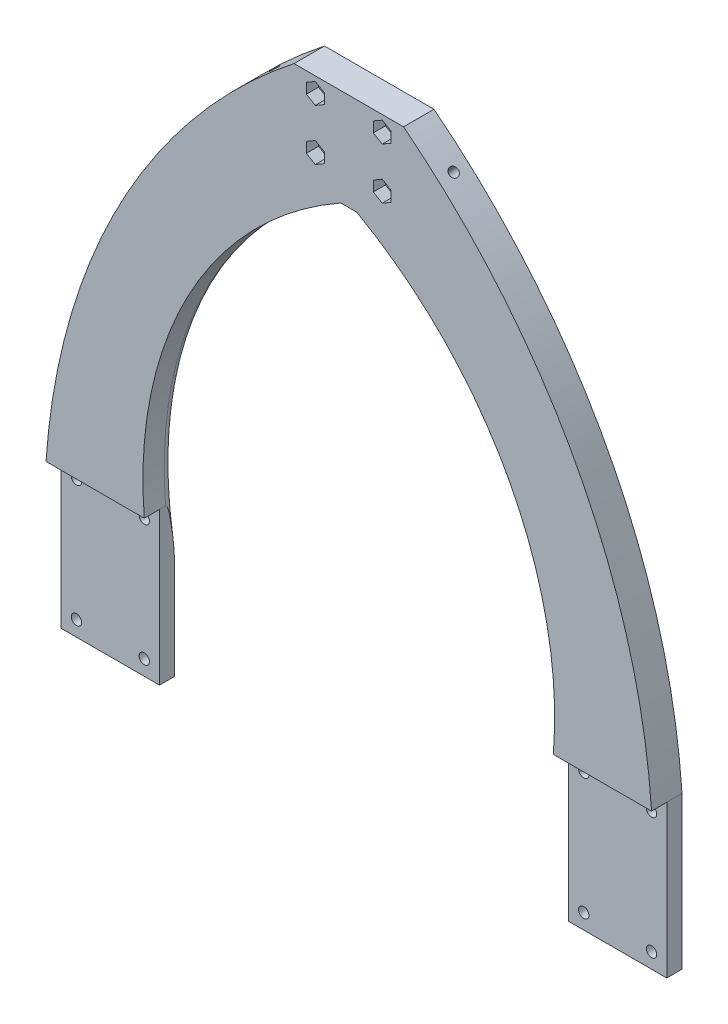
SolidWorks part; units mm, degrees
ref_plane "Ebene vorne" through (0, 0, 0) normal (0, 0, 1) x (1, 0, 0)
ref_plane "Ebene oben" through (0, 0, 0) normal (0, 1, 0) x (1, 0, 0)
ref_plane "Ebene rechts" through (0, 0, 0) normal (1, 0, 0) x (0, 0, -1)
sketch "Skizze1" plane through (0, 0, 0) normal (0, 1, 0) x (1, 0, 0)
  line L1 (-99.5, -210) -> (99.5, -210)
  line L2 (-99.5, -210) -> (-99.5, 210)
  line L3 (-99.5, 210) -> (99.5, 210)
  line L4 (99.5, -210) -> (99.5, 210)
  line L5 (-99.5, -210) -> (99.5, 210) construction
  line L6 (-99.5, 210) -> (99.5, -210) construction
  point P0 (0, 0)
  dimension "D1" = 199
  dimension "D2" = 420
extrude "Aufsatz-Linear austragen1" add sketch "Skizze1" along normal blind 10
ref_plane "Ebene1" through (0, -97.5366, 81.8429) normal (0, -0.766, 0.6428) x (1, 0, 0)
sketch "Skizze2" plane through (0, -97.5366, 81.8429) normal (0, -0.766, 0.6428) x (1, 0, 0)
  line L1 (-99.5, 167.2972) -> (99.5, 167.2972) construction
  circle A0 centre (0, 147.2972) radius 5
  dimension "D1" = 10
  dimension "D2" = 20
extrude "Schnitt-Linear austragen1" [suppressed] cut sketch "Skizze2" against normal blind 30 and the other way blind 10
sketch "Skizze3" [suppressed] plane through (0, -67.9923, 57.0523) normal (0, -0.766, 0.6428) x (1, 0, 0)
  circle A0 centre (0, 101.3345) radius 5
  dimension "D1" = 10
extrude "Aufsatz-Linear austragen2" [suppressed] add sketch "Skizze3" along normal blind 0.1
sketch "Skizze4" plane through (0, -97.5366, 81.8429) normal (0, -0.766, 0.6428) x (1, 0, 0)
  line L0 (0, 167.2972) -> (0, 159.9002) construction
  line L1 (-99.5, 167.2972) -> (99.5, 167.2972) construction
  line L2 (-25, 167.2972) -> (-25, 202.2972)
  line L3 (-25, 202.2972) -> (25, 202.2972)
  line L4 (-25, 167.2972) -> (25, 167.2972)
  line L5 (25, 167.2972) -> (25, 202.2972)
  point P10 (0, 202.2972)
  dimension "D1" = 50
  dimension "D2" = 35
extrude "Aufsatz-Linear austragen3" [suppressed] add sketch "Skizze4" against normal blind 10 separate body
sketch "Skizze5" plane through (0, 10, 0) normal (0, 1, 0) x (1, 0, 0)
  line L0 (0, 0) -> (0, -210) construction
  line L1 (-99.5, -210) -> (99.5, -210) construction
  line L2 (99.5, -210) -> (18, -210)
  line L3 (-18, -210) -> (-99.5, -56)
  line L4 (-99.5, 210) -> (-99.5, -210) construction
  line L5 (-99.5, -56) -> (-99.5, -210)
  line L6 (-99.5, -210) -> (-18, -210)
  line L7 (99.5, -56) -> (99.5, -210)
  line L8 (18, -210) -> (99.5, -56)
  line L9 (-99.5, 210) -> (-99.5, 125)
  line L10 (-99.5, 125) -> (99.5, 125)
  line L11 (99.5, -210) -> (99.5, 210) construction
  line L12 (99.5, 125) -> (99.5, 210)
  line L13 (99.5, 210) -> (-99.5, 210)
  line L14 (67.211, -56) -> (-67.211, -56)
  line L15 (-67.211, -56) -> (-2.6461, -178)
  line L16 (67.211, -56) -> (2.6461, -178)
  line L17 (-2.6461, -178) -> (2.6461, -178)
  line L18 (2.6461, -178) -> (0, -183) construction
  line L19 (-2.6461, -178) -> (0, -183) construction
  point P27 (0, -56)
  dimension "D1" = 36
  dimension "D2" = 154
  dimension "D3" = 85
  dimension "D4" = 32
  dimension "D5" = 27
extrude "Schnitt-Linear austragen2" cut sketch "Skizze5" against normal blind 10
sketch "Skizze6" plane through (0, 10, 0) normal (0, 1, 0) x (1, 0, 0)
  line L0 (0, -210) -> (0, -178) construction
  line L1 (-18, -210) -> (18, -210) construction
  line L2 (-2.6461, -178) -> (2.6461, -178) construction
  line L3 (0, -196.59) -> (-21.075, -196.59) construction
  circle A0 centre (-11, -205) radius 1.7
  circle A1 centre (-11, -188.18) radius 1.7
  circle A2 centre (11, -205) radius 1.7
  circle A3 centre (11, -188.18) radius 1.7
  dimension "D1" = 3.4
  dimension "D2" = 11
  dimension "D3" = 5
  dimension "D4" = 13.41
extrude "Schnitt-Linear austragen3" cut sketch "Skizze6" against normal through all
sketch "Skizze7" plane through (0, 0, 0) normal (0, -1, 0) x (1, 0, 0)
  line L0 (-11, 205) -> (-11, 210) construction
  line L1 (-18, 210) -> (18, 210) construction
  line L2 (-11, 205) -> (-5.1092, 205) construction
  line L3 (-11, 208.4064) -> (-8.05, 206.7032)
  line L4 (-8.05, 206.7032) -> (-8.05, 203.2968)
  line L5 (-11, 201.5936) -> (-8.05, 203.2968)
  line L6 (-11, 201.5936) -> (-13.95, 203.2968)
  line L7 (-13.95, 206.7032) -> (-13.95, 203.2968)
  line L8 (-11, 208.4064) -> (-13.95, 206.7032)
  line L9 (0, 210) -> (0, 121.6034) construction
  line L10 (11, 205) -> (11, 188.18) construction
  line L11 (11, 196.59) -> (0, 196.59) construction
  line L12 (11, 208.4064) -> (8.05, 206.7032)
  line L13 (11, 201.5936) -> (8.05, 203.2968)
  line L14 (8.05, 206.7032) -> (8.05, 203.2968)
  line L15 (11, 201.5936) -> (13.95, 203.2968)
  line L16 (13.95, 206.7032) -> (13.95, 203.2968)
  line L17 (11, 208.4064) -> (13.95, 206.7032)
  line L18 (-8.05, 186.4768) -> (-8.05, 189.8832)
  line L19 (-11, 191.5864) -> (-13.95, 189.8832)
  line L20 (-11, 191.5864) -> (-8.05, 189.8832)
  line L21 (-13.95, 186.4768) -> (-13.95, 189.8832)
  line L22 (-11, 184.7736) -> (-13.95, 186.4768)
  line L23 (-11, 184.7736) -> (-8.05, 186.4768)
  line L24 (8.05, 186.4768) -> (8.05, 189.8832)
  line L25 (11, 191.5864) -> (8.05, 189.8832)
  line L26 (11, 191.5864) -> (13.95, 189.8832)
  line L27 (13.95, 186.4768) -> (13.95, 189.8832)
  line L28 (11, 184.7736) -> (13.95, 186.4768)
  line L29 (11, 184.7736) -> (8.05, 186.4768)
  point P10 (-8.05, 205)
  dimension "D1" = 120
  dimension "D2" = 5.9
extrude "Schnitt-Linear austragen4" cut sketch "Skizze7" against normal blind 4
sketch "Skizze8" plane through (0, 10, 0) normal (0, 1, 0) x (1, 0, 0)
  line L0 (99.5, 115.41) -> (78.872, 115.41) construction
  line L1 (99.5, -56) -> (99.5, 125) construction
  line L2 (-99.5, 125) -> (99.5, 125) construction
  dimension "D1" = 9.59
ref_plane "Ebene2" through (0, 62.6966, -52.6087) normal (0, 0.766, -0.6428) x (-1, 0, 0)
sketch "Skizze9" plane through (0, 62.6966, -52.6087) normal (0, 0.766, -0.6428) x (-1, 0, 0)
  line L0 (-99.5, -81.9813) -> (-78.872, -81.9813) construction
  line L1 (-99.5, 49.3264) -> (-99.5, -89.3277) construction
  line L2 (0, -45.2589) -> (0, -16.2619) construction
  circle A0 centre (-94.5, -81.9813) radius 1.7
  circle A1 centre (94.5, -81.9813) radius 1.7
  circle A2 centre (-30, -81.9813) radius 1.7
  circle A3 centre (30, -81.9813) radius 1.7
  dimension "D1" = 3.4
  dimension "D2" = 5
  dimension "D3" = 30
extrude "Schnitt-Linear austragen5" [suppressed] cut sketch "Skizze9" against normal through all and the other way through all
ref_plane "Ebene3" through (0, 55.0361, -46.1808) normal (0, 0.766, -0.6428) x (-1, 0, 0)
sketch "Skizze10" [suppressed] plane through (0, 55.0361, -46.1808) normal (0, 0.766, -0.6428) x (-1, 0, 0)
  line L0 (-95, -81.9813) -> (-100, -81.9813) construction
  line L1 (-95, -81.9813) -> (-95, -30.0694) construction
  line L2 (-95, -78.7482) -> (-97.8, -80.3647)
  line L3 (-97.8, -80.3647) -> (-97.8, -83.5979)
  line L4 (-95, -85.2145) -> (-97.8, -83.5979)
  line L5 (-95, -85.2145) -> (-92.2, -83.5979)
  line L6 (-92.2, -80.3647) -> (-92.2, -83.5979)
  line L7 (-95, -78.7482) -> (-92.2, -80.3647)
  line L8 (0, 0) -> (0, -45.6283) construction
  line L9 (-30, -81.9813) -> (-95, -81.9813) construction
  line L10 (-62.5, -81.9813) -> (-62.5, -23.1343) construction
  line L11 (-32.8, -80.3647) -> (-32.8, -83.5979)
  line L12 (-30, -85.2145) -> (-32.8, -83.5979)
  line L13 (-30, -85.2145) -> (-27.2, -83.5979)
  line L14 (-27.2, -80.3647) -> (-27.2, -83.5979)
  line L15 (-30, -78.7482) -> (-27.2, -80.3647)
  line L16 (-30, -78.7482) -> (-32.8, -80.3647)
  line L17 (95, -78.7482) -> (92.2, -80.3647)
  line L18 (92.2, -80.3647) -> (92.2, -83.5979)
  line L19 (95, -85.2145) -> (92.2, -83.5979)
  line L20 (95, -85.2145) -> (97.8, -83.5979)
  line L21 (97.8, -80.3647) -> (97.8, -83.5979)
  line L22 (95, -78.7482) -> (97.8, -80.3647)
  line L23 (30, -78.7482) -> (32.8, -80.3647)
  line L24 (30, -78.7482) -> (27.2, -80.3647)
  line L25 (27.2, -80.3647) -> (27.2, -83.5979)
  line L26 (30, -85.2145) -> (27.2, -83.5979)
  line L27 (30, -85.2145) -> (32.8, -83.5979)
  line L28 (32.8, -80.3647) -> (32.8, -83.5979)
  point P9 (-97.8, -81.9813)
  point P31 (97.8, -81.9813)
  dimension "D1" = 120
  dimension "D2" = 5.6
extrude "Schnitt-Linear austragen6" [suppressed] cut sketch "Skizze10" against normal blind 10 and the other way blind 5
sketch "Skizze13" plane through (0, 10, 0) normal (0, 1, 0) x (1, 0, 0)
  line L0 (67.211, -56) -> (99.5, -56) construction
  line L1 (67.211, -56) -> (92.4353, -69.3492) construction
  line L2 (99.5, -56) -> (18, -210) construction
  line L3 (0, 0) -> (0, -38.1435) construction
  line L4 (2.6461, -178) -> (67.211, -56) construction
  line L5 (79.8232, -62.6746) -> (103.8351, -17.3024) construction
  line L6 (99.5, -56) -> (99.5, 125) construction
  line L7 (83.3555, -56) -> (83.3555, -1) construction
  line L8 (93.5, -58.8065) -> (101.0692, -44.504) construction
  line L9 (83.1285, -86.935) -> (57.9043, -73.5858) construction
  line L10 (71.7911, -80.935) -> (86.3039, -80.935) construction
  circle A0 centre (93.5, -58.8065) radius 1.7
  circle A1 centre (72.5142, -58.8065) radius 1.7
  circle A2 centre (81.7891, -80.935) radius 1.7
  circle A3 centre (-81.7891, -80.935) radius 1.7
  circle A4 centre (-93.5, -58.8065) radius 1.7
  circle A5 centre (-72.5142, -58.8065) radius 1.7
  dimension "D1" = 6
  dimension "D5" = 35
  dimension "D3" = 3.4
  dimension "D6" = 3.4
  dimension "D2" = 6
  dimension "D4" = 6
extrude "Schnitt-Linear austragen7" [suppressed] cut sketch "Skizze13" against normal through all
sketch "Skizze14" plane through (100.8819, 0, 53.3888) normal (0.8839, 0, 0.4678) x (0.4678, 0, -0.8839)
  line L0 (-37.9543, 5) -> (-37.9543, 10)
  line L5 (-2.9543, 0) -> (-2.9543, 10) construction
  line L6 (-37.9543, 5) -> (-2.9543, 5)
  line L7 (-2.9543, 10) -> (-177.1905, 10) construction
  line L8 (-37.9543, 10) -> (-2.9543, 10)
  line L9 (-2.9543, 10) -> (-2.9543, 5)
  dimension "D1" = 35
extrude "Schnitt-Linear austragen8" [suppressed] cut sketch "Skizze14" against normal up to surface (28.9525 mm away)
mirror "Spiegeln1" [suppressed] about plane through (0, 0, 0) normal (1, 0, 0)
sketch "Skizze15" [suppressed] plane through (95, 0, 0) normal (1, 0, 0) x (0, 0, -1)
  line L0 (4, 10) -> (4, 0)
  line L1 (4, 0) -> (65, 0)
  line L2 (65, 0) -> (65, 10)
  line L3 (65, 10) -> (4, 10)
extrude "Schnitt-Linear austragen9" [suppressed] cut sketch "Skizze15" against normal through all
sketch "Skizze16" plane through (0, 0, 0) normal (0, -1, 0) x (1, 0, 0)
  line L0 (0, 210) -> (0, 178) construction
  line L1 (-18, 210) -> (18, 210) construction
  line L2 (-2.6461, 178) -> (2.6461, 178) construction
  line L3 (11, 196.59) -> (0, 196.59) construction
  line L4 (11, 205) -> (11, 188.18) construction
  line L6 (-17.5, 193.09) -> (17.5, 193.09)
  line L7 (-17.5, 193.09) -> (-17.5, 200.09)
  line L8 (-17.5, 200.09) -> (17.5, 200.09)
  line L9 (17.5, 193.09) -> (17.5, 200.09)
  line L10 (-17.5, 193.09) -> (17.5, 200.09) construction
  line L11 (-17.5, 200.09) -> (17.5, 193.09) construction
  dimension "D1" = 7
  dimension "D2" = 35
extrude "Schnitt-Linear austragen10" [suppressed] cut sketch "Skizze16" against normal blind 5
sketch "Skizze17" [suppressed] plane through (17.5, 0, 0) normal (-1, 0, 0) x (0, 0, 1)
  line L0 (196.59, 0) -> (196.59, 11.1261) construction
  line L1 (193.09, 0) -> (200.09, 0) construction
  line L2 (193.09, 5) -> (196.59, 8.5)
  line L3 (196.59, 8.5) -> (200.09, 5)
  line L4 (200.09, 5) -> (193.09, 5)
  dimension "D1" = 90
extrude "Schnitt-Linear austragen11" [suppressed] cut sketch "Skizze17" along normal up to surface (35 mm away)
sketch "Skizze18" [suppressed] plane through (0, 10, 0) normal (0, 1, 0) x (1, 0, 0)
  line L0 (0, -210) -> (0, 0) construction
  line L1 (-18, -210) -> (18, -210) construction
  line L2 (62.5765, -72.2325) -> (35.4483, -67.5372)
  line L3 (15.3378, -155.8503) -> (-22.1774, -134.6566)
  line L4 (2.8247, -178) -> (62.5765, -72.2325) construction
  line L5 (-15.3378, -155.8503) -> (22.1774, -134.6566)
  line L6 (58.6594, -79.166) -> (40.7308, -76.063)
  line L7 (0, -147.1854) -> (19.5429, -147.1854) construction
  line L8 (0, -95.4) -> (31.4297, -95.4) construction
  line L9 (11.6488, -162.3803) -> (0, -155.7995)
  line L10 (-71.7468, -56) -> (-2.8247, -178) construction
  line L11 (0, -95.4) -> (-37.5153, -116.5937) construction
  line L12 (-37.5153, -116.5937) -> (-39.2566, -117.5774) construction
  line L13 (-11.6488, -162.3803) -> (0, -155.7995)
  line L14 (-58.6594, -79.166) -> (-40.7308, -76.063)
  line L15 (-62.5765, -72.2325) -> (-35.4483, -67.5372)
  circle A0 centre (0, -95.4) radius 33.5
  arc A1 (7.4594, -151.3994) -> (7.4594, -142.9713) centre (9.84, -147.1854) cw
  arc A2 (-7.4594, -151.3994) -> (-7.4594, -142.9713) centre (-9.84, -147.1854) ccw
  circle A3 centre (0, -95.4) radius 45.0879
  point P17 (0, -147.1854)
  point P36 (5, -147.1854)
  point P40 (-5, -147.1854)
  line M16 (62.5765, -72.2325) -> (2.8247, -178)
  line M18 (-2.8247, -178) -> (-71.7468, -56)
  dimension "D2" = 67
  dimension "D5" = 2
  dimension "D4" = 10
  dimension "D1" = 114.6
  dimension "D3" = 7.5
  dimension "D6" = 7.5
extrude "Aufsatz-Linear austragen4" [suppressed] add sketch "Skizze18" against normal blind 10 contours A3 L15 L14 M18 | A3 A0 M16 M18 | A3 L6 L2 M16 | A2 L5 L3 | A3 L3 L5 | L3 A1 L5 | L13 L9 L3 L5 M18 M16
sketch "Skizze19" [suppressed] plane through (0, 0, 0) normal (0, -1, 0) x (1, 0, 0)
  circle A0 centre (0, 35.4) radius 31.5
  circle A1 centre (0, 35.4) radius 33.5
  circle A2 centre (0, 35.4) radius 33.5 construction
  dimension "D1" = 63
extrude "Aufsatz-Linear austragen5" [suppressed] add sketch "Skizze19" against normal blind 1
sketch "Skizze20" plane through (0, 10, 0) normal (0, 1, 0) x (1, 0, 0)
  line L0 (99.5, 119.52) -> (55.4083, 119.52) construction
  line L1 (99.5, -56) -> (99.5, 125) construction
  line L2 (-99.5, 125) -> (99.5, 125) construction
  line L3 (0, 125) -> (0, 96.9732) construction
  line L4 (105, 43.82) -> (35.5869, 43.82) construction
  circle A0 centre (90.5, 119.52) radius 1.7
  circle A1 centre (48.5, 119.52) radius 1.7
  circle A2 centre (-48.5, 119.52) radius 1.7
  circle A3 centre (-90.5, 119.52) radius 1.7
  circle A4 centre (87, 43.82) radius 1.7
  circle A5 centre (52, 43.82) radius 1.7
  circle A6 centre (-87, 43.82) radius 1.7
  circle A7 centre (-52, 43.82) radius 1.7
  dimension "D1" = 3.4
  dimension "D2" = 5.48
  dimension "D3" = 9
  dimension "D4" = 42
  dimension "D5" = 75.7
  dimension "D6" = 12.5
  dimension "D7" = 35
extrude "Schnitt-Linear austragen12" cut sketch "Skizze20" against normal through all
sketch "Skizze21" plane through (0, 10, 0) normal (0, 1, 0) x (1, 0, 0)
  line L0 (-67.211, -56) -> (-67.211, 19)
  line L1 (-67.211, 19) -> (67.211, 19)
  line L2 (67.211, 19) -> (67.211, -56)
  line L3 (67.211, -56) -> (-67.211, -56) construction
  line L4 (-67.211, -56) -> (67.211, -56)
  dimension "D1" = 75
extrude "Schnitt-Linear austragen13" cut sketch "Skizze21" against normal through all
sketch "Skizze22" plane through (0, 10, 0) normal (0, 1, 0) x (1, 0, 0)
  line L0 (-67.211, -56) -> (-2.6461, -178)
  arc A0 (-67.211, -56) -> (-2.6461, -178) centre (60.0769, -66.7211) ccw
  line M19 (-2.6461, -178) -> (-67.211, -56)
extrude "Schnitt-Linear austragen14" cut sketch "Skizze22" against normal through all contours M19 region at (-42.1385, 10, 120.8156)
sketch "Skizze23" plane through (0, 10, 0) normal (0, 1, 0) x (1, 0, 0)
  line L0 (-18, -210) -> (-99.5, -56) construction
  line L1 (-99.5, -56) -> (-18, -210)
  arc A0 (-18, -210) -> (-99.5, -56) centre (114.4449, -41.3416) cw
  arc A2 (-67.211, -56) -> (-2.6461, -178) centre (60.0769, -66.7211) ccw construction
  dimension "D1" = 60
extrude "Aufsatz-Linear austragen6" add sketch "Skizze23" against normal blind 10
mirror "Spiegeln2" about plane through (0, 0, 0) normal (1, 0, 0) of "Aufsatz-Linear austragen6", "Schnitt-Linear austragen14"
sketch "Skizze25" plane through (0, 10, 0) normal (0, 1, 0) x (1, 0, 0)
  line L0 (-99.5, -56) -> (-67.211, -56) construction
  line L1 (-99.5, -6) -> (-99.5, -56) construction
  line L2 (-99.5, -6) -> (-67.211, -6) construction
  line L3 (-67.211, 19) -> (-67.211, -56) construction
  line L4 (-83.3555, -6) -> (-83.3555, -56) construction
  line L5 (-99.5, -31) -> (-67.211, -31) construction
  line L6 (-99.5, 125) -> (-99.5, -56) construction
  circle A0 centre (-94.5, -11) radius 1.7
  circle A1 centre (-72.211, -11) radius 1.7
  circle A2 centre (-72.211, -51) radius 1.7
  circle A3 centre (-94.5, -51) radius 1.7
  dimension "D2" = 3.4
  dimension "D1" = 50
  dimension "D3" = 5
  dimension "D4" = 5
extrude "Schnitt-Linear austragen15" cut sketch "Skizze25" against normal through all
sketch "Skizze26" plane through (-99.5, 0, 0) normal (-1, 0, 0) x (0, 0, 1)
  line L0 (56, 5) -> (56, 0)
  line L1 (56, 0) -> (56, 10) construction
  line L2 (56, 5) -> (6, 5)
  line L3 (6, 5) -> (6, 10)
  line L4 (-125, 0) -> (56, 0) construction
  line L5 (5.0128, 19.5087) -> (6, 10)
  line L6 (5.0128, 19.5087) -> (-137.7077, 19.5087)
  line L7 (-137.7077, 19.5087) -> (-137.7077, -14.4017)
  line L8 (-137.7077, -14.4017) -> (4.1968, -14.4017)
  line L9 (4.1968, -14.4017) -> (56, 0)
  line L10 (-125, 10) -> (56, 10) construction
mirror "Spiegeln3" about plane through (0, 0, 0) normal (1, 0, 0) of "Schnitt-Linear austragen15"
extrude "Schnitt-Linear austragen16" cut sketch "Skizze26" against normal through all
fillet "Verrundung1" radius 3 3 edges at (52.8259, 10, 126.4716) (-52.8259, 10, 126.4716) (0, 10, 178)
sketch "Skizze27" plane through (0, 0, 0) normal (0, -1, 0) x (1, 0, 0)
  line L0 (18, 210) -> (40.2407, 189.8666) construction
  arc A0 (99.5, 56) -> (18, 210) centre (-114.4449, 41.3416) ccw construction
  dimension "D1" = 30
ref_plane "Ebene4" through (112.589, 0, 124.3732) normal (0.6711, 0, 0.7414) x (0.7414, 0, -0.6711)
sketch "Skizze28" plane through (112.589, 0, 124.3732) normal (0.6711, 0, 0.7414) x (0.7414, 0, -0.6711)
  line L0 (-112.5893, 0) -> (-112.5893, 10) construction
  line L1 (-127.5893, 0) -> (-97.5893, 0) construction
  line L2 (36.1825, 10) -> (-127.5893, 10) construction
  circle A0 centre (-112.5893, 5) radius 1.5
  dimension "D1" = 3
extrude "Schnitt-Linear austragen17" cut sketch "Skizze28" against normal blind 8 and the other way blind 10
mirror "Spiegeln4" about plane through (0, 0, 0) normal (1, 0, 0) of "Schnitt-Linear austragen17"
move or copy body "Körper-Verschieben/Kopieren1" bodies to move or copy 127 copy no rotation origin (0, 5.338, 108) rotation axis (-1, 0, 0) rotation angle 90
